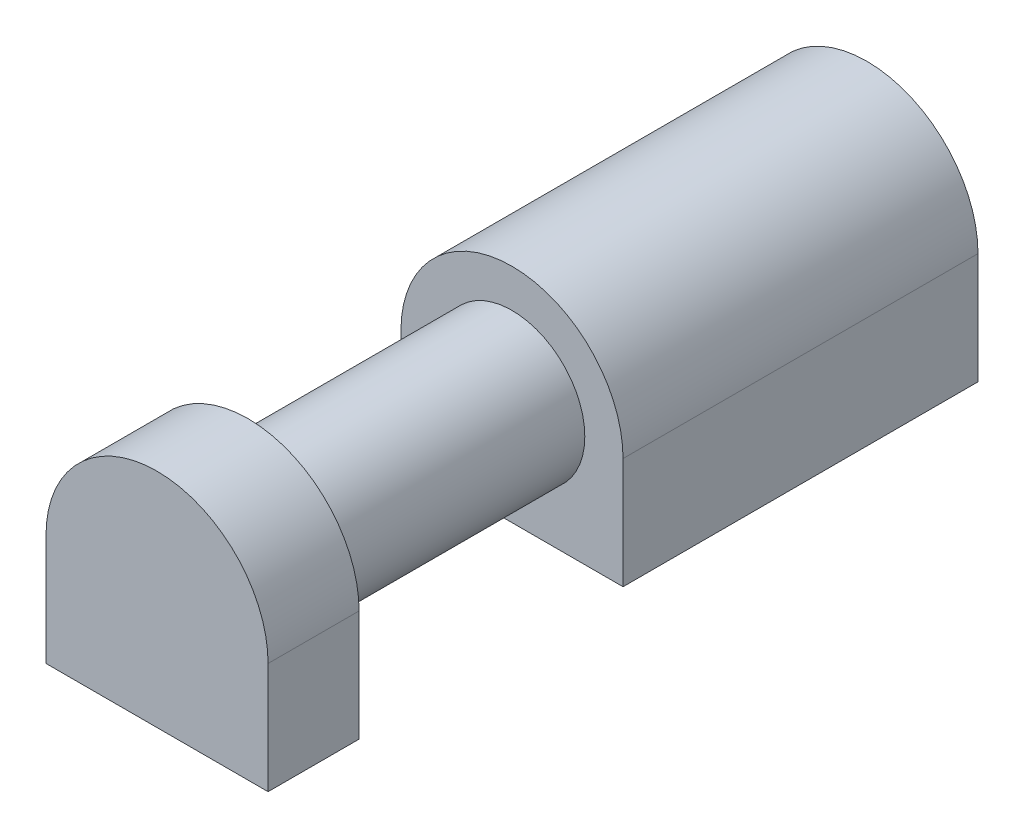
SolidWorks part; units mm, degrees
ref_plane "Front Plane" through (0, 0, 0) normal (0, 0, 1) x (1, 0, 0)
ref_plane "Top Plane" through (0, 0, 0) normal (0, 1, 0) x (1, 0, 0)
ref_plane "Right Plane" through (0, 0, 0) normal (1, 0, 0) x (0, 0, -1)
sketch "Sketch1" plane through (0, 0, 0) normal (0, 0, 1) x (1, 0, 0)
  circle A0 centre (0, 0) radius 4.25
  circle A1 centre (0, 0) radius 6.1
  dimension "D1" = 8.5
  dimension "D2" = 12.2
extrude "Boss-Extrude1" add sketch "Sketch1" along normal blind 12
sketch "Sketch2" plane through (0, 0, 12) normal (0, 0, 1) x (1, 0, 0)
  circle A0 centre (0, 0) radius 6.1
  circle A1 centre (0, 0) radius 6.1 construction
  dimension "D1" = 0
extrude "Boss-Extrude2" add sketch "Sketch2" along normal blind 2
sketch "Sketch3" plane through (0, 0, 14) normal (0, 0, 1) x (1, 0, 0)
  circle A0 centre (0, 0) radius 4
  dimension "D1" = 8
extrude "Boss-Extrude3" add sketch "Sketch3" along normal blind 20
sketch "Sketch4" plane through (0, 0, 34) normal (0, 0, 1) x (1, 0, 0)
  circle A0 centre (0, 0) radius 6.1
  dimension "D1" = 12.2
extrude "Boss-Extrude4" add sketch "Sketch4" along normal blind 5
sketch "Sketch5" plane through (0, 0, 14) normal (0, 0, 1) x (1, 0, 0)
  circle A0 centre (0, 0) radius 6.1
  circle A1 centre (0, 0) radius 6.1 construction
extrude "Boss-Extrude5" add sketch "Sketch5" along normal blind 5.5
sketch "Sketch6" plane through (0, 0, 39) normal (0, 0, 1) x (1, 0, 0)
  line L0 (-6.1, 0) -> (-6.1, -6.1)
  line L1 (-6.1, -6.1) -> (6.1, -6.1)
  line L2 (0, -6.1) -> (0, 6.1) construction
  line L3 (6.1, 0) -> (6.1, -6.1)
  arc A0 (6.1, 0) -> (-6.1, 0) centre (0, 0) ccw
  circle A1 centre (0, 0) radius 6.1 construction
extrude "Boss-Extrude6" add sketch "Sketch6" against normal up to surface (5 mm away) up to face at (4, 0, 34)
sketch "Sketch7" plane through (0, 0, 0) normal (0, 0, -1) x (-1, 0, 0)
  line L0 (-6.1, 0) -> (-6.1, -6.1)
  line L1 (-6.1, -6.1) -> (6.1, -6.1)
  line L2 (6.1, -6.1) -> (6.1, 0)
  line L3 (6.1, 0) -> (4.25, 0)
  line L4 (-4.25, 0) -> (-6.1, 0)
  arc A1 (-4.25, 0) -> (4.25, 0) centre (0, 0) ccw
  circle A2 centre (0, 0) radius 4.25 construction
extrude "Boss-Extrude7" add sketch "Sketch7" against normal up to surface (19.5 mm away) up to face at (4, 0, 19.5)
